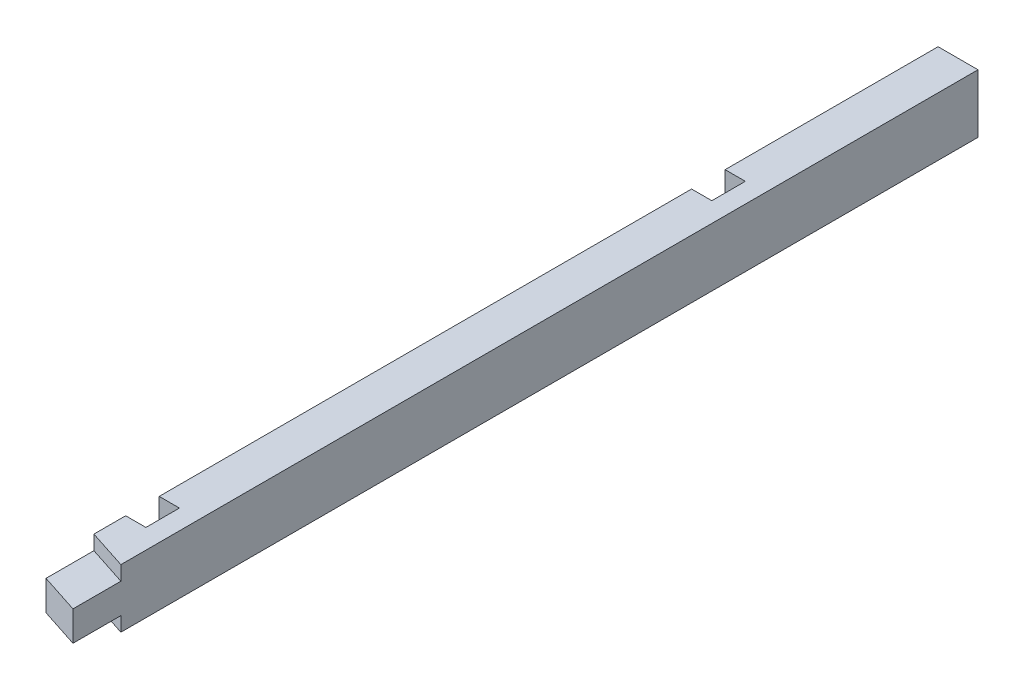
SolidWorks part; units mm, degrees
ref_plane "Front" through (0, 0, 0) normal (0, 0, 1) x (1, 0, 0)
ref_plane "Top" through (0, 0, 0) normal (0, 1, 0) x (1, 0, 0)
ref_plane "Right" through (0, 0, 0) normal (1, 0, 0) x (0, 0, -1)
sketch "Esquisse1" plane through (0, 0, 0) normal (0, 0, 1) x (1, 0, 0)
  line L1 (0, 0) -> (75, 0)
  line L2 (0, 0) -> (0, 110)
  line L3 (0, 110) -> (75, 110)
  line L4 (75, 0) -> (75, 110)
  dimension "D1" = 75
  dimension "D2" = 110
extrude "Boss.-Extru.1" add sketch "Esquisse1" along normal blind 1700
sketch "Esquisse3" plane through (0, 0, 0) normal (-1, 0, 0) x (0, 0, 1)
  line L0 (1700, 55) -> (1660.3905, 55) construction
  line L1 (1700, 110) -> (1610, 110)
  line L2 (1700, 110) -> (1700, 0) construction
  line L3 (1610, 0) -> (1610, 27)
  line L4 (1700, 110) -> (1700, 83)
  line L5 (1700, 83) -> (1610, 83)
  line L6 (1610, 110) -> (1610, 83)
  line L8 (1700, 27) -> (1610, 27)
  line L9 (1700, 0) -> (1700, 27)
  line L10 (1700, 0) -> (1610, 0)
  dimension "D1" = 90
  dimension "D2" = 27
extrude "Enlèv. mat.-Extru.1" cut sketch "Esquisse3" against normal through all
sketch "Esquisse4" plane through (0, 0, 0) normal (0, -1, 0) x (1, 0, 0)
  line L0 (75, 1610) -> (0, 1585.631)
  line L1 (0, 1610) -> (0, 0) construction
  line L3 (0, 1585.631) -> (0, 1610)
  line L4 (0, 1610) -> (75, 1610)
  dimension "D1" = 18
extrude "Enlèv. mat.-Extru.2" cut sketch "Esquisse4" against normal up to vertex (27 mm away) up to point (75, 27, 1700)
sketch "Esquisse5" plane through (0, 0, 0) normal (-1, 0, 0) x (0, 0, 1)
  line L0 (1585.631, 0) -> (0, 0) construction
  line L1 (1463, 0) -> (1526, 0)
  line L2 (1463, 0) -> (1463, 110)
  line L3 (1463, 110) -> (1526, 110)
  line L4 (1526, 0) -> (1526, 110)
  line L5 (1610, 110) -> (0, 110) construction
  line L6 (0, 110) -> (0, 0) construction
  line L7 (400, 110) -> (463, 110)
  line L8 (400, 110) -> (400, 0)
  line L9 (400, 0) -> (463, 0)
  line L10 (463, 110) -> (463, 0)
  point P12 (400, 55)
  dimension "D1" = 63
  dimension "D2" = 63
  dimension "D3" = 400
  dimension "D4" = 1000
extrude "Enlèv. mat.-Extru.4" cut sketch "Esquisse5" against normal blind 38
extrude "Enlèv. mat.-Extru.5" cut sketch "Esquisse4<3>" along normal up to vertex (-83 mm away) from vertex up to point (75, 83, 1610) starting at point (75, 110, 1610)
sketch "Esquisse4<3>" plane through (0, 0, 0) normal (0, -1, 0) x (1, 0, 0) same geometry as "Esquisse4"
sketch "Esquisse6" plane through (0, 27, 0) normal (0, -1, 0) x (1, 0, 0)
  line L0 (75, 1700) -> (0, 1700)
  line L1 (75, 1700) -> (75, 1610) construction
  line L2 (0, 1700) -> (0, 1675.631)
  line L3 (0, 1700) -> (0, 1585.631) construction
  line L4 (0, 1675.631) -> (75, 1700)
  line L5 (75, 1700) -> (0, 1700) construction
  line L6 (0, 1585.631) -> (75, 1610) construction
extrude "Enlèv. mat.-Extru.6" cut sketch "Esquisse6" against normal through all
sketch "Esquisse8" [suppressed] plane through (0, 10, 0) normal (0, -1, 0) x (1, 0, 0)
  line L0 (75, 2200) -> (0, 2200)
  line L1 (0, 2200) -> (0, 2175.631)
  line L2 (0, 2200) -> (0, 2085.631) construction
  line L3 (0, 2175.631) -> (75, 2200)
  line L4 (0, 2085.631) -> (75, 2110) construction
extrude "Enlèv. mat.-Extru.7" [suppressed] cut sketch "Esquisse8" against normal through all
